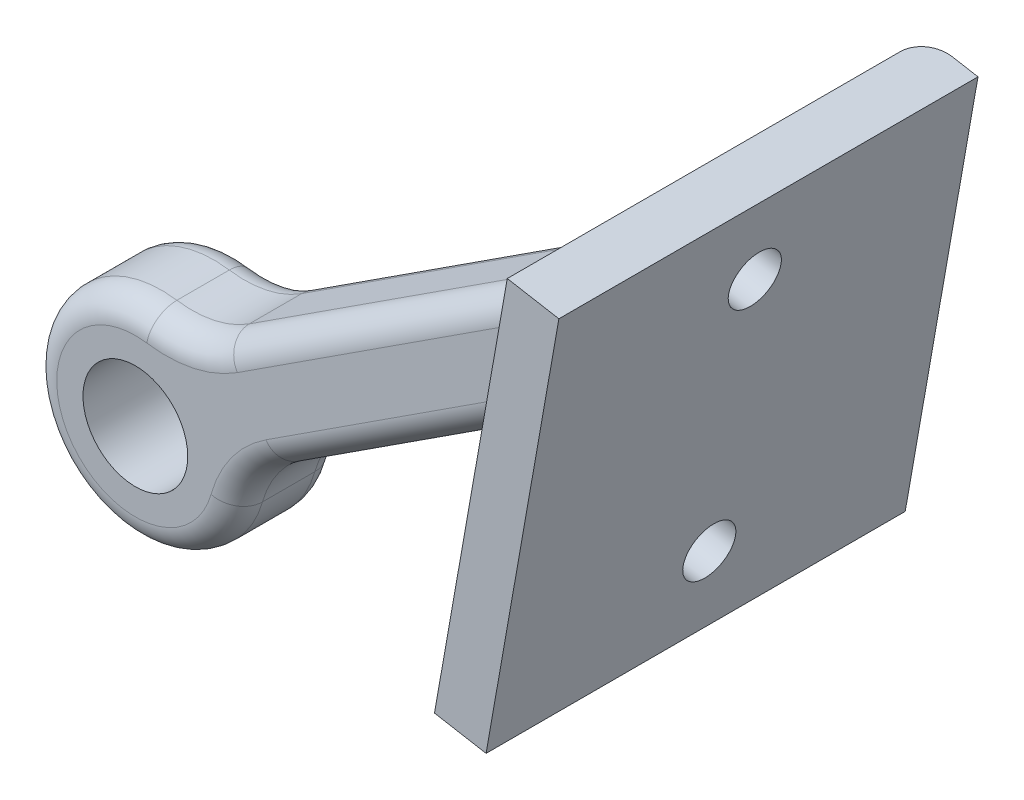
SolidWorks part; units mm, degrees
material "Cast Alloy Steel"
ref_plane "Front" through (0, 0, 0) normal (0, 0, 1) x (1, 0, 0)
ref_plane "Top" through (0, 0, 0) normal (0, 1, 0) x (1, 0, 0)
ref_plane "Right" through (0, 0, 0) normal (1, 0, 0) x (0, 0, -1)
sketch "Sketch1" plane through (0, 0, 0) normal (0, 0, 1) x (1, 0, 0)
  line L0 (0, 0) -> (25.4, 144.0506) construction
  line L1 (25.4, 144.0506) -> (25.4, 0) construction
  line L2 (25.4, 0) -> (0, 0) construction
  line L3 (4.4107, 25.0141) -> (-1.8429, 26.1168)
  line L4 (-1.8429, 26.1168) -> (6.9785, 76.145)
  line L5 (6.9785, 76.145) -> (13.232, 75.0424)
  line L6 (13.232, 75.0424) -> (4.4107, 25.0141)
  line L7 (-76.2, 0) -> (2.5678, 51.1309) construction
  circle A0 centre (-76.2, 0) radius 12.7
  dimension "D1" = 25.4
  dimension "D2" = 76.2
  dimension "D3" = 50.8
  dimension "D4" = 25.4
  dimension "D5" = 6.35
  dimension "D6" = 10
  dimension "D7" = 25.4
sketch "Sketch2" plane through (0, 0, 0) normal (0, 0, 1) x (1, 0, 0)
  line L0 (-1.8429, 26.1168) -> (6.9785, 76.145) construction
  line L1 (1.0604, 42.5818) -> (4.0752, 59.68)
  line L2 (-56.7711, 12.612) -> (60.7287, 88.8851) construction
  line L3 (-76.2, 0) -> (2.5678, 51.1309) construction
  line L4 (-70.4321, 11.3147) -> (4.0752, 59.68)
  line L5 (-63.5173, 0.6622) -> (1.0604, 42.5818)
  circle A0 centre (-76.2, 0) radius 12.7 construction
  arc A1 (-70.4321, 11.3147) -> (-63.5173, 0.6622) centre (-76.2, 0) ccw
  dimension "D1" = 12.7
extrude "Base-Extrude" add sketch "Sketch2" along normal blind 12.7
sketch "Sketch3" plane through (0, 0, 0) normal (0, 0, 1) x (1, 0, 0)
  line L4 (4.4107, 25.0141) -> (-1.8429, 26.1168)
  line L5 (13.232, 75.0424) -> (4.4107, 25.0141)
  line L6 (6.9785, 76.145) -> (13.232, 75.0424)
  line L7 (-1.8429, 26.1168) -> (6.9785, 76.145)
  line L8 (4.4107, 25.0141) -> (-1.8429, 26.1168)
  line L9 (13.232, 75.0424) -> (4.4107, 25.0141)
  line L10 (6.9785, 76.145) -> (13.232, 75.0424)
  line L11 (-1.8429, 26.1168) -> (6.9785, 76.145)
  dimension "D1" = 0
extrude "Boss-Extrude1" add sketch "Sketch3" along normal blind 50.8
fillet "Fillet1" radius 12.7 2 edges at (-63.5173, 0.6622, 6.35) (-70.4321, 11.3147, 6.35)
sketch "Sketch5" plane through (-6.2535, 1.1027, 0) normal (-0.9848, 0.1736, 0) x (0, 0, 1)
  line L0 (25.4, 76.2) -> (25.4, 25.4) construction
  line L1 (50.8, 76.2) -> (0, 76.2) construction
  line L2 (50.8, 25.4) -> (0, 25.4) construction
  circle A0 centre (25.4, 66.675) radius 3.175
  circle A1 centre (25.4, 34.925) radius 3.175
  dimension "D3" = 6.35
  dimension "D4" = 6.35
  dimension "D1" = 9.525
  dimension "D2" = 9.525
extrude "Cut-Extrude2" cut sketch "Sketch5" against normal through all
fillet "Fillet4" radius 9.525 2 edges at (4.0752, 59.68, 6.35) (1.0604, 42.5818, 6.35)
fillet "Fillet5" radius 3.175 15 edges at (3.3566, 60.1558, 12.7) (-7.6778, 32.3485, 0) (-32.4826, 35.9491, 12.7) (-37.4064, 17.6117, 0) (-69.7784, 12.717, 12.7) (-61.9703, 0.6885, 0) (-86.8524, -6.9149, 12.7) (-86.8524, -6.9149, 0) (5.8865, 69.9524, 0) (-61.9703, 0.6885, 12.7) (-7.6778, 32.3485, 12.7) (-69.7784, 12.717, 0) (3.3566, 60.1558, 0) (-37.4064, 17.6117, 12.7) (-32.4826, 35.9491, 0)
sketch "Sketch6" plane through (0, 0, 12.7) normal (0, 0, 1) x (1, 0, 0)
  circle A0 centre (-76.2, 0) radius 6.35
  dimension "D1" = 12.7
extrude "Cut-Extrude3" cut sketch "Sketch6" against normal through all
fillet "Fillet6" radius 1.5875 3 edges at (-1.6488, 27.2176, 11.3088) (3.8228, 58.2485, 12.236) (1.195, 43.3451, 12.7)
